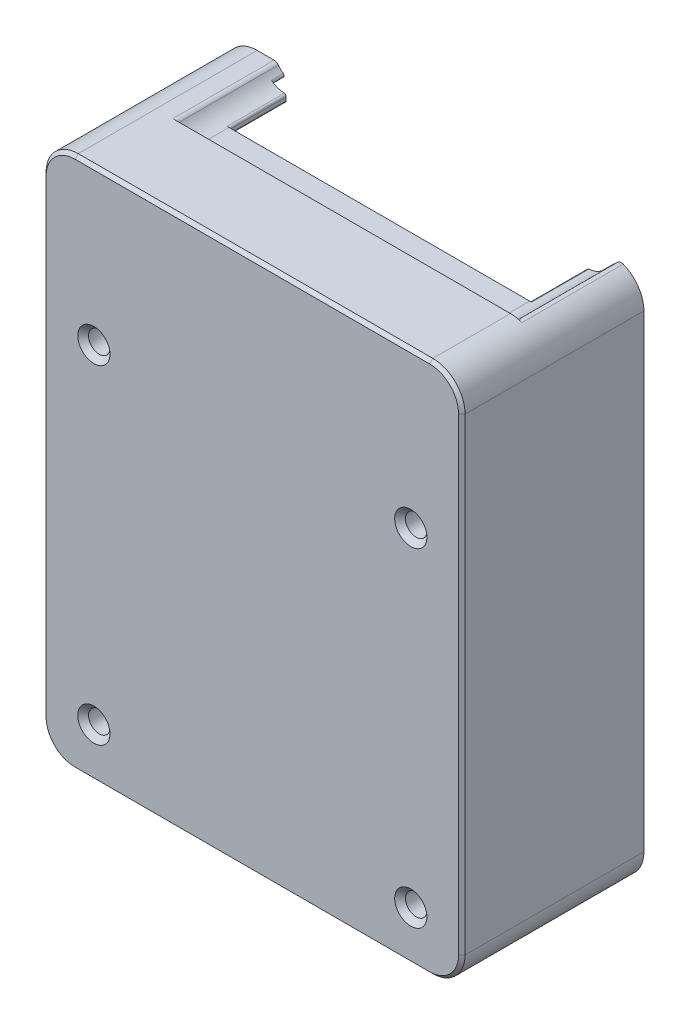
SolidWorks part; units mm, degrees
ref_plane "Спереди(Плоскость XY)" through (0, 0, 0) normal (0, 0, 1) x (1, 0, 0)
ref_plane "Сверху(Плоскость XZ)" through (0, 0, 0) normal (0, 1, 0) x (1, 0, 0)
ref_plane "Справа(Плоскость ZY)" through (0, 0, 0) normal (1, 0, 0) x (0, 0, -1)
sketch "Эскиз1" plane through (0, 0, 0) normal (0, 0, 1) x (1, 0, 0)
  line L4 (33.9096, -45.9) -> (0.9096, -45.9) construction
  line L5 (-0.9904, -44) -> (-0.9904, -1) construction
  line L6 (0.9096, 0.9) -> (33.9096, 0.9) construction
  line L7 (35.8096, -1) -> (35.8096, -44) construction
  line L8 (33.8096, -46.4) -> (1.0096, -46.4)
  line L9 (-1.1904, -44.2) -> (-1.1904, -0.8)
  line L10 (1.0096, 1.4) -> (33.8096, 1.4)
  line L11 (36.0096, -0.8) -> (36.0096, -44.2)
  line L12 (33.9096, -47.3) -> (0.9096, -47.3)
  line L13 (36.9096, -0.7) -> (36.9096, -44.3)
  line L14 (0.9096, 2.3) -> (33.9096, 2.3)
  line L15 (-2.0904, -44.3) -> (-2.0904, -0.7)
  line L16 (5.4596, -45.9) -> (0.9096, -45.9) construction
  line L17 (-0.9904, -44) -> (-0.9904, -1) construction
  line L18 (35.8096, -1) -> (35.8096, -44) construction
  line L19 (0.5657, 0.9) -> (3.4898, 0.9) construction
  arc A4 (-0.9904, -44) -> (0.9096, -45.9) centre (0.9096, -44) ccw construction
  arc A5 (0.9096, 0.9) -> (-0.9904, -1) centre (0.9096, -1) ccw construction
  arc A6 (35.8096, -1) -> (33.9096, 0.9) centre (33.9096, -1) ccw construction
  arc A7 (33.9096, -45.9) -> (35.8096, -44) centre (33.9096, -44) ccw construction
  arc A8 (-1.1904, -44.2) -> (1.0096, -46.4) centre (1.0096, -44.2) ccw
  arc A9 (1.0096, 1.4) -> (-1.1904, -0.8) centre (1.0096, -0.8) ccw
  arc A10 (36.0096, -0.8) -> (33.8096, 1.4) centre (33.8096, -0.8) ccw
  arc A11 (33.8096, -46.4) -> (36.0096, -44.2) centre (33.8096, -44.2) ccw
  arc A12 (-2.0904, -44.3) -> (0.9096, -47.3) centre (0.9096, -44.3) ccw
  arc A13 (33.9096, -47.3) -> (36.9096, -44.3) centre (33.9096, -44.3) ccw
  arc A14 (36.9096, -0.7) -> (33.9096, 2.3) centre (33.9096, -0.7) ccw
  arc A15 (0.9096, 2.3) -> (-2.0904, -0.7) centre (0.9096, -0.7) ccw
  arc A16 (0.9096, 0.9) -> (-0.9904, -1) centre (0.9096, -1) ccw construction
  arc A17 (35.8096, -1) -> (33.9292, 0.8999) centre (33.9096, -1) ccw construction
  arc A18 (33.9096, -45.9) -> (35.8096, -44) centre (33.9096, -44) ccw construction
  arc A19 (-0.9904, -44) -> (0.9096, -45.9) centre (0.9096, -44) ccw construction
  dimension "D7" = 2.2
  dimension "D8" = 3
  dimension "D3" = 0.5
  dimension "D1" = 0.2
  dimension "D2" = 0.2
  dimension "D4" = 0.5
  dimension "D5" = 0.9
  dimension "D6" = 0.9
  dimension "D9" = 0.9
  dimension "D10" = 0.9
extrude "Бобышка-Вытянуть1" add sketch "Эскиз1" against normal blind 2.45
sketch "Эскиз2" plane through (0, 0, 0) normal (0, 0, 1) x (1, 0, 0)
  line L0 (0.9096, -47.3) -> (33.9096, -47.3) construction
  line L1 (-2.0904, -0.7) -> (-2.0904, -44.3) construction
  line L2 (33.9096, 2.3) -> (0.9096, 2.3) construction
  line L3 (36.9096, -44.3) -> (36.9096, -0.7) construction
  line L4 (0.9096, -47.3) -> (33.9096, -47.3)
  line L5 (-2.0904, -0.7) -> (-2.0904, -44.3)
  line L6 (33.9096, 2.3) -> (0.9096, 2.3)
  line L7 (36.9096, -44.3) -> (36.9096, -0.7)
  line L8 (5.4596, -42.7) -> (5.4596, -46.4)
  line L9 (2.6596, -39.9) -> (-2.0904, -39.9)
  line L10 (2.6596, -14.9) -> (-1.1904, -14.9)
  line L11 (2.6596, -9.3) -> (-1.1904, -9.3)
  line L12 (29.3596, -42.7) -> (29.3596, -46.4)
  line L13 (32.1596, -39.9) -> (36.0096, -39.9)
  line L14 (-1.1904, -0.8) -> (-1.1904, -44.2) construction
  line L15 (-1.1904, -0.8) -> (-1.1904, -9.3)
  line L16 (-1.1904, -14.9) -> (-1.1904, -39.9)
  line L17 (33.8096, 1.4) -> (1.0096, 1.4) construction
  line L19 (1.0096, -46.4) -> (33.8096, -46.4) construction
  line L20 (33.8096, 1.4) -> (1.0096, 1.4)
  line L21 (36.0096, -44.2) -> (36.0096, -0.8) construction
  line L22 (5.4596, -46.4) -> (29.3596, -46.4)
  line L23 (36.0096, -39.9) -> (36.0096, -0.8)
  arc A1 (0.9096, 2.3) -> (-2.0904, -0.7) centre (0.9096, -0.7) ccw construction
  arc A2 (36.9096, -0.7) -> (33.9096, 2.3) centre (33.9096, -0.7) ccw construction
  arc A3 (5.4596, -42.7) -> (2.6596, -39.9) centre (2.6596, -42.7) ccw
  arc A4 (2.6596, -14.9) -> (2.6596, -9.3) centre (2.6596, -12.1) ccw
  circle A5 centre (32.1596, -42.7) radius 2.8
  arc A6 (-2.0904, -44.3) -> (0.9096, -47.3) centre (0.9096, -44.3) ccw construction
  arc A9 (33.9096, -47.3) -> (36.9096, -44.3) centre (33.9096, -44.3) ccw construction
  arc A10 (-2.0904, -44.3) -> (0.9096, -47.3) centre (0.9096, -44.3) ccw
  arc A11 (0.9096, 2.3) -> (-2.0904, -0.7) centre (0.9096, -0.7) ccw
  arc A12 (36.9096, -0.7) -> (33.9096, 2.3) centre (33.9096, -0.7) ccw
  arc A13 (33.9096, -47.3) -> (36.9096, -44.3) centre (33.9096, -44.3) ccw
  arc A14 (1.0096, 1.4) -> (-1.1904, -0.8) centre (1.0096, -0.8) ccw construction
  arc A15 (36.0096, -0.8) -> (33.8096, 1.4) centre (33.8096, -0.8) ccw construction
  arc A16 (1.0096, 1.4) -> (-1.1904, -0.8) centre (1.0096, -0.8) ccw
  arc A17 (36.0096, -0.8) -> (33.8096, 1.4) centre (33.8096, -0.8) ccw
  circle A18 centre (2.6596, -42.7) radius 1
  circle A19 centre (2.6596, -12.1) radius 1
  circle A20 centre (32.1596, -42.7) radius 1
  dimension "D1" = 2
extrude "Бобышка-Вытянуть2" add sketch "Эскиз2" along normal blind 13.5
cosmetic thread "Условное изображение резьбы1" parameters "D2"=2.5
cosmetic thread "Условное изображение резьбы3" parameters "D2"=2.5
cosmetic thread "Условное изображение резьбы4" parameters "D2"=2.5
sketch "Эскиз3" plane through (0, 0, 13.5) normal (0, 0, 1) x (1, 0, 0)
  line L4 (-2.0904, -0.7) -> (-2.0904, -44.3)
  line L5 (0.9096, -47.3) -> (33.9096, -47.3)
  line L6 (36.9096, -44.3) -> (36.9096, -0.7)
  line L7 (33.9096, 2.3) -> (0.9096, 2.3)
  line L8 (-2.0904, -0.7) -> (-2.0904, -44.3)
  line L9 (0.9096, -47.3) -> (33.9096, -47.3)
  line L10 (36.9096, -44.3) -> (36.9096, -0.7)
  line L11 (33.9096, 2.3) -> (0.9096, 2.3)
  circle A0 centre (2.6596, -42.7) radius 1 construction
  circle A1 centre (2.6596, -12.1) radius 1 construction
  circle A2 centre (32.1596, -42.7) radius 1 construction
  circle A3 centre (2.6596, -42.7) radius 1
  arc A4 (-2.0904, -44.3) -> (0.9096, -47.3) centre (0.9096, -44.3) ccw
  arc A5 (-2.0904, -44.3) -> (0.9096, -47.3) centre (0.9096, -44.3) ccw
  arc A6 (33.9096, -47.3) -> (36.9096, -44.3) centre (33.9096, -44.3) ccw
  arc A7 (33.9096, -47.3) -> (36.9096, -44.3) centre (33.9096, -44.3) ccw
  arc A8 (0.9096, 2.3) -> (-2.0904, -0.7) centre (0.9096, -0.7) ccw
  arc A9 (0.9096, 2.3) -> (-2.0904, -0.7) centre (0.9096, -0.7) ccw
  arc A10 (36.9096, -0.7) -> (33.9096, 2.3) centre (33.9096, -0.7) ccw
  arc A11 (36.9096, -0.7) -> (33.9096, 2.3) centre (33.9096, -0.7) ccw
  circle A12 centre (2.6596, -12.1) radius 1
  circle A13 centre (32.1596, -42.7) radius 1
  dimension "D1" = 0
extrude "Бобышка-Вытянуть3" add sketch "Эскиз3" along normal blind 1
sketch "Эскиз4" plane through (0, -47.3, 0) normal (0, -1, 0) x (1, 0, 0)
  line L0 (17.4096, 2.35) -> (17.4096, 14.5) construction
  line L1 (5.4596, -2.85) -> (29.3596, -2.85)
  line L2 (5.4596, -2.85) -> (5.4596, 2.35)
  line L3 (5.4596, 2.35) -> (29.3596, 2.35)
  line L4 (29.3596, -2.85) -> (29.3596, 2.35)
  line L5 (0.9096, 14.5) -> (33.9096, 14.5) construction
  dimension "D1" = 5.2
  dimension "D2" = 12.15
  dimension "D3" = 23.9
extrude "Вырез-Вытянуть1" cut sketch "Эскиз4" against normal blind 4
sketch "Эскиз5" plane through (0, 2.3, 0) normal (0, 1, 0) x (1, 0, 0)
  line L1 (32.7096, 2.8237) -> (4.7096, 2.8237)
  line L2 (32.7096, 2.8237) -> (32.7096, -3.9763)
  line L3 (32.7096, -3.9763) -> (4.7096, -3.9763)
  line L4 (4.7096, 2.8237) -> (4.7096, -3.9763)
  dimension "D1" = 6.8
extrude "Вырез-Вытянуть2" cut sketch "Эскиз5" against normal blind 4
sketch "Эскиз6" plane through (0, 0, 14.5) normal (0, 0, 1) x (1, 0, 0)
  line L0 (32.1596, -12.1) -> (2.6596, -12.1) construction
  line L1 (32.1596, -12.1) -> (32.1596, -42.7) construction
  circle A0 centre (32.1596, -12.1) radius 1
  circle A1 centre (2.6596, -12.1) radius 1 construction
extrude "Вырез-Вытянуть3" cut sketch "Эскиз6" against normal blind 10
cosmetic thread "Условное изображение резьбы2" parameters "D2"=2.5
sketch "Эскиз8" plane through (0, 0, 13.5) normal (0, 0, -1) x (-1, 0, 0)
  line L0 (-32.1596, -9.3) -> (-36.0096, -9.3)
  line L1 (-36.0096, -44.2) -> (-36.0096, -0.8) construction
  line L2 (-36.0096, -9.3) -> (-36.0096, -14.9)
  line L3 (-36.0096, -0.8) -> (-36.0096, -39.9) construction
  line L4 (-36.0096, -14.9) -> (-32.1596, -14.9)
  arc A0 (-32.1596, -14.9) -> (-32.1596, -9.3) centre (-32.1596, -12.1) ccw
  arc A1 (-2.6596, -9.3) -> (-2.6596, -14.9) centre (-2.6596, -12.1) ccw construction
  circle A2 centre (-32.1596, -12.1) radius 1 construction
  circle A3 centre (-32.1596, -12.1) radius 1
extrude "Бобышка-Вытянуть4" add sketch "Эскиз8" along normal blind 6
ref_plane "Плоскость1" through (0, 0, -1.35) normal (0, 0, -1) x (-1, 0, 0)
sketch "Эскиз13" plane through (0, 0, -2.45) normal (0, 0, -1) x (-1, 0, 0)
  line L0 (-1.0096, 1.4) -> (-33.8096, 1.4) construction
  line L1 (1.1904, -9.3) -> (1.1904, -0.8) construction
  line L2 (-36.0096, -0.8) -> (-36.0096, -9.3) construction
  line L3 (-29.3596, -46.4) -> (-33.8096, -46.4) construction
  line L4 (-1.0096, 1.4) -> (-4.7096, 1.4)
  line L5 (1.1904, -44.2) -> (1.1904, -0.8)
  line L6 (-36.0096, -0.8) -> (-36.0096, -44.2)
  line L7 (-1.0096, -46.4) -> (-5.4596, -46.4)
  line L8 (-32.7096, 1.4) -> (-33.8096, 1.4)
  line L10 (-4.7096, 1.4) -> (-1.0096, 1.4) construction
  line L11 (-29.3596, -46.4) -> (-33.8096, -46.4)
  line L12 (-5.4596, -46.4) -> (-5.4596, -47.3) construction
  arc A0 (-33.8096, 1.4) -> (-36.0096, -0.8) centre (-33.8096, -0.8) ccw construction
  arc A1 (1.1904, -0.8) -> (-1.0096, 1.4) centre (-1.0096, -0.8) ccw construction
  arc A2 (-36.0096, -44.2) -> (-33.8096, -46.4) centre (-33.8096, -44.2) ccw construction
  arc A3 (-1.0096, -46.4) -> (1.1904, -44.2) centre (-1.0096, -44.2) ccw construction
  arc A4 (-33.8096, 1.4) -> (-36.0096, -0.8) centre (-33.8096, -0.8) ccw
  arc A5 (1.1904, -0.8) -> (-1.0096, 1.4) centre (-1.0096, -0.8) ccw
  arc A6 (-36.0096, -44.2) -> (-33.8096, -46.4) centre (-33.8096, -44.2) ccw
  arc A7 (-1.0096, -46.4) -> (1.1904, -44.2) centre (-1.0096, -44.2) ccw
extrude "Вытянуть-Тонкостенный1" add sketch "Эскиз13" against normal up to surface (15.95 mm away) thin up to face at (17.4096, -21.5664, 13.5) thin type one direction reverse wall 0.1
sketch "Эскиз14" plane through (0, 0, 3.9763) normal (0, 0, -1) x (-1, 0, 0)
  line L0 (-4.7096, 1.4) -> (-32.7096, 1.4) construction
  line L1 (-4.7096, 1.4) -> (-32.7096, 1.4)
extrude "Вытянуть-Тонкостенный2" add sketch "Эскиз14" against normal up to surface (9.5237 mm away) thin up to face at (17.6263, -17.7571, 13.5) thin type one direction reverse wall 0.1
sketch "Эскиз15" plane through (0, 0, 2.35) normal (0, 0, -1) x (-1, 0, 0)
  line L0 (-29.3596, -46.4) -> (-5.4596, -46.4) construction
  line L1 (-29.3596, -46.4) -> (-5.4596, -46.4)
extrude "Вытянуть-Тонкостенный3" add sketch "Эскиз15" against normal up to surface (11.15 mm away) thin up to face at (17.4096, -21.5785, 13.5) thin type one direction reverse wall 0.1
sketch "Эскиз9" plane through (0, 0, -1.35) normal (0, 0, -1) x (-1, 0, 0)
  line L0 (-0.81, -46.2905) -> (-2.8758, -46.2905)
  line L1 (0.5443, -45.6126) -> (-0.1217, -45.0072) construction
  line L2 (1.0904, -44.2) -> (1.0904, -42.1489)
  line L3 (-35.9096, -0.8) -> (-35.9096, -9.3) construction
  line L4 (-32.1596, -42.7) -> (-2.6596, -42.7) construction
  line L5 (-17.4096, -42.7) -> (-17.4096, -36.7934) construction
  line L6 (-35.9096, -44.2) -> (-35.9096, -42.1489)
  line L7 (-34.0091, -46.2905) -> (-31.9434, -46.2905)
  line L8 (1.0904, -44.2) -> (-0.1217, -45.0072) construction
  line L9 (-32.7096, 0.5) -> (-33.3096, 0.5)
  line L10 (-32.7096, 1.2) -> (-32.7096, 0.5)
  line L11 (-32.7096, 1.2) -> (-33.9096, 1.2) construction
  line L12 (-0.1217, -45.0072) -> (-0.81, -46.2905) construction
  line L13 (-35.1096, -1.3) -> (-35.1096, -1.7)
  line L14 (-35.8096, -0.7) -> (-35.8096, -1.7) construction
  line L15 (-1.5096, 0.5) -> (-4.7096, 0.5)
  line L16 (-0.9096, 1.2) -> (-4.7096, 1.2) construction
  line L17 (-32.7096, 1.2) -> (-32.7096, 2.3)
  line L18 (-35.8096, -1.7) -> (2.5867, -1.7) construction
  line L19 (0.9904, -0.7) -> (0.7552, -1.7) construction
  line L20 (-35.1096, -1.7) -> (-35.8096, -1.7) construction
  line L21 (-4.7096, 1.2) -> (-4.7096, 0.5)
  line L22 (-4.7096, 2.3) -> (-32.7096, 2.3) construction
  line L25 (0.2904, -1.7) -> (0.2904, -1.3)
  line L26 (-32.7096, 2.3) -> (-33.9096, 2.3)
  line L27 (1.0904, -44.2) -> (1.0904, -0.8) construction
  line L28 (-35.9096, -3.3) -> (-36.9096, -0.7)
  line L29 (1.0904, -3.3) -> (2.0904, -0.7)
  line L30 (-0.9096, 2.3) -> (-4.7096, 2.3)
  line L31 (-4.7096, 2.3) -> (-4.7096, 1.2)
  line L32 (1.0904, -39.9) -> (1.0904, -44.2) construction
  arc A1 (-0.81, -46.2905) -> (1.0904, -44.2) centre (-1.0096, -44.2) ccw
  arc A2 (-2.8758, -46.2905) -> (-1.4115, -45.6528) centre (-2.8758, -44.2905) ccw
  arc A3 (-1.4115, -45.6528) -> (0.3985, -43.6619) centre (-1.6015, -43.6619) ccw
  arc A4 (0.3985, -43.6619) -> (1.0904, -42.1489) centre (-0.9096, -42.1489) ccw
  arc A5 (-33.3096, 0.5) -> (-35.1096, -1.3) centre (-33.3096, -1.3) ccw
  arc A6 (-33.9096, 1.2) -> (-35.8096, -0.7) centre (-33.9096, -0.7) ccw construction
  arc A7 (0.9904, -0.7) -> (-0.9096, 1.2) centre (-0.9096, -0.7) ccw construction
  arc A8 (0.2904, -1.3) -> (-1.5096, 0.5) centre (-1.5096, -1.3) ccw
  arc A9 (-35.1096, -1.7) -> (-35.9096, -3.3) centre (-33.9096, -3.3) ccw
  arc A10 (1.0904, -3.3) -> (0.2904, -1.7) centre (-0.9096, -3.3) ccw
  arc A11 (-35.2176, -43.6619) -> (-35.9096, -42.1489) centre (-33.9096, -42.1489) cw
  arc A12 (-33.9096, 2.3) -> (-36.9096, -0.7) centre (-33.9096, -0.7) ccw construction
  arc A13 (-33.9096, 2.3) -> (-36.9096, -0.7) centre (-33.9096, -0.7) ccw
  arc A14 (2.0904, -0.7) -> (-0.9096, 2.3) centre (-0.9096, -0.7) ccw construction
  arc A15 (2.0904, -0.7) -> (-0.9096, 2.3) centre (-0.9096, -0.7) ccw
  arc A16 (-35.2176, -43.6619) -> (-33.4077, -45.6528) centre (-33.2176, -43.6619) ccw
  arc A17 (-31.9434, -46.2905) -> (-33.4077, -45.6528) centre (-31.9434, -44.2905) cw
  arc A18 (-34.0091, -46.2905) -> (-35.9096, -44.2) centre (-33.8096, -44.2) cw
  arc A19 (-1.0096, -46.3) -> (1.0904, -44.2) centre (-1.0096, -44.2) ccw construction
  dimension "D2" = 4
  dimension "D4" = 4
  dimension "D3" = 0.9
  dimension "D5" = 2
  dimension "D7" = 2
  dimension "D1" = 4
extrude "Бобышка-Вытянуть5" add sketch "Эскиз9" against normal up to surface (14.85 mm away) up to face at (17.4096, -21.5685, 13.5)
sketch "Эскиз12" plane through (0, 0, 3.9763) normal (0, 0, -1) x (-1, 0, 0)
  line L1 (-32.7096, 2.3) -> (-4.7096, 2.3)
  line L2 (-32.7096, 2.3) -> (-32.7096, 0.5)
  line L3 (-32.7096, 0.5) -> (-4.7096, 0.5)
  line L4 (-4.7096, 2.3) -> (-4.7096, 0.5)
extrude "Бобышка-Вытянуть6" add sketch "Эскиз12" against normal up to surface (9.5237 mm away) up to face at (17.5953, -15.7252, 13.5)
sketch "Эскиз11" plane through (0, 0, -2.45) normal (0, 0, -1) x (-1, 0, 0)
  line L0 (-35.01, 3.5004) -> (-2.4092, 3.5004)
  line L1 (-32.7096, 1.2) -> (-4.7096, 1.2)
  arc A4 (-4.7096, 1.2) -> (-2.4092, 3.5004) centre (-4.7096, 3.5004) ccw
  arc A5 (-35.01, 3.5004) -> (-32.7096, 1.2) centre (-32.7096, 3.5004) ccw
  dimension "D1" = 2.3004
extrude "Вырез-Вытянуть4" cut sketch "Эскиз11" against normal offset from surface (9.4263 mm away) 3 up to face at (18.7096, 1.4, 3.9763) offset beyond the face yes
fillet "Скругление1" radius 0.5 8 edges at (34.6175, 2.2153, 2.2632) (2.7472, 2.3, 2.2632) (-0.2904, -1.7, 6.075) (35.1096, -1.7, 6.075) (1.4115, -45.6528, -0.675) (-0.3985, -43.6619, -0.675) (33.4077, -45.6528, -0.675) (35.2176, -43.6619, -0.675)
fillet "Скругление2" radius 0.2 11 edges at (29.3596, -47.3, -0.05) (5.4596, -47.3, -0.05) (29.3596, -46.3, -1.225) (5.4596, -46.3, -1.225) (33.8096, 1.3, -1.9) (4.7096, 0.5, 1.3132) (32.7096, 0.5, 1.3132) (32.7096, 1.2, 1.3132) (33.3805, 1.3, -1.9) (4.0387, 1.3, -1.9) (4.7096, 1.2, 1.3132)
fillet "Скругление3" radius 1.5 6 edges at (35.9096, -39.9, 6.75) (29.3596, -46.3, 7.925) (5.4596, -46.3, 7.925) (-1.0904, -39.9, 6.75) (-1.0904, -9.3, 6.75) (-1.0904, -14.9, 6.75)
fillet "Скругление4" radius 2 2 edges at (35.9096, -14.9, 10.5) (35.9096, -9.3, 10.5)
chamfer "Фаска1" distance 0.3 angle 45 8 edges at (36.0309, -46.4213, 14.5) (36.9096, -22.5, 14.5) (17.4096, -47.3, 14.5) (36.0309, 1.4213, 14.5) (-1.2117, -46.4213, 14.5) (17.4096, 2.3, 14.5) (-2.0904, -22.5, 14.5) (-1.2117, 1.4213, 14.5)
chamfer "Фаска2" distance 0.5 angle 45 4 edges at (3.6596, -42.7, 14.5) (33.1596, -42.7, 14.5) (3.6596, -12.1, 14.5) (33.1596, -12.1, 14.5)
